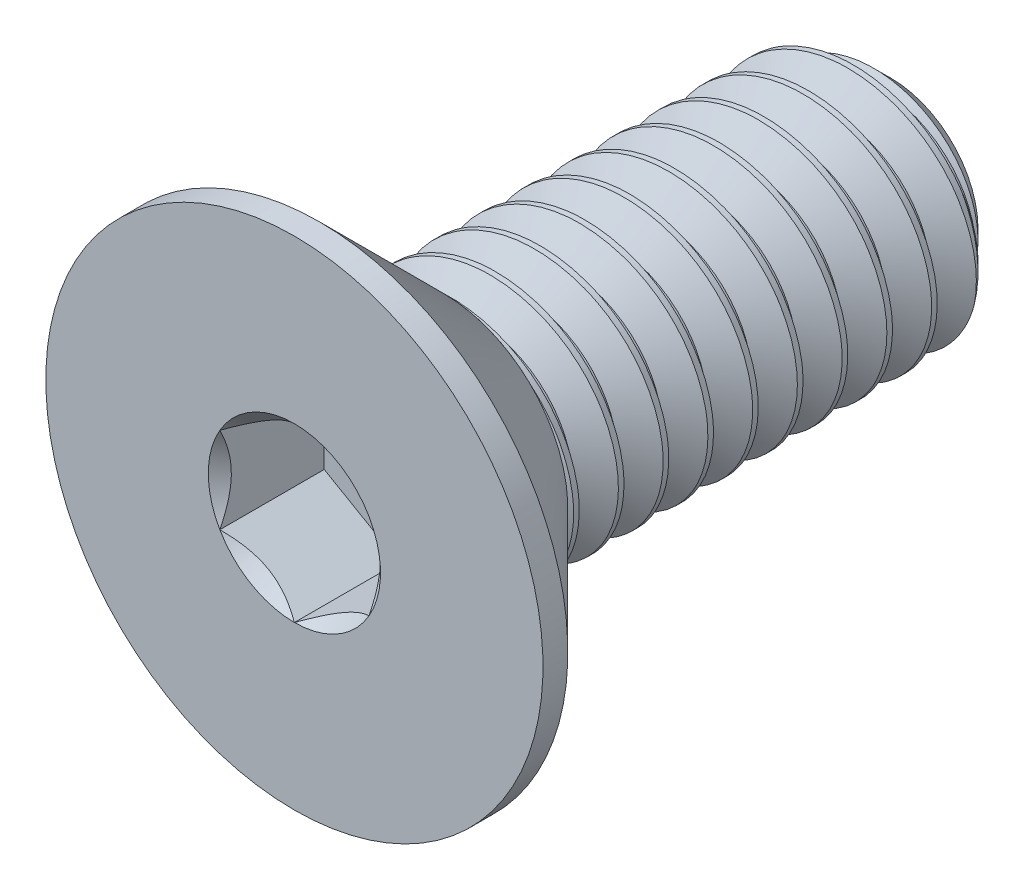
SolidWorks part; units mm, degrees
ref_plane "Front" through (0, 0, 0) normal (0, 0, 1) x (1, 0, 0)
ref_plane "Top" through (0, 0, 0) normal (0, 1, 0) x (1, 0, 0)
ref_plane "Right" through (0, 0, 0) normal (1, 0, 0) x (0, 0, -1)
sketch "Sketch1" plane through (0, 0, 0) normal (1, 0, 0) x (0, 0, -1)
  line L0 (-3, 2.5) -> (-2.75, 2.5) construction
  line L1 (-2.75, 2.5) -> (-1.5, 1.25) construction
  line L2 (-3, 1.25) -> (3, 1.25) construction
  line L3 (3, 1.25) -> (3, 0) construction
  line L4 (3, 0) -> (-3, 0) construction
  line L5 (-3, 0) -> (-3, 2.5) construction
  line L6 (-3, 2.5) -> (-3, -2.5) construction
  line L7 (3, 1.25) -> (3, -1.25) construction
  line L8 (-3, -2.5) -> (-2.75, -2.5) construction
  line L9 (-2.75, -2.5) -> (-1.5, -1.25) construction
  line L11 (-3, 1.25) -> (-3, 0) construction
  line L12 (-1.5, 1.25) -> (-1.5, 0) construction
  line L13 (2.9719, 1.2987) -> (3.1969, 0.909) construction
  line L14 (3.1969, 0.909) -> (3.4219, 1.2987) construction
  line L15 (3.4219, 1.2987) -> (2.9719, 1.2987) construction
  line L16 (3.1969, 1.2987) -> (3.1969, 1.25) construction
  line L17 (3.1969, 1.25) -> (3.1969, 0.9577) construction
  line L18 (3.1969, 0.9577) -> (3.1969, 0.909) construction
  line L19 (3.1969, 1.2744) -> (3.4078, 1.2744) construction
  line L20 (3.1969, 1.2744) -> (2.9859, 1.2744) construction
  line L21 (3, 1.25) -> (3.3938, 1.25) construction
  line L22 (3.1688, 0.9577) -> (3.225, 0.9577) construction
  line L23 (3, -1.25) -> (-1.5, -1.25) construction
  point P10 (1.875, -1.25)
  point P24 (-1.5, 1.25)
  point P30 (0, 0)
  dimension "Head Diameter" = 5
  dimension "Head Height" = 1.5
  dimension "Length" = 6
  dimension "Countersink Angle" = 90
  dimension "Thread Pitch" = 0.45
  dimension "D2" = 0.0563
  dimension "Minimum Thread Length" = 4.5
  dimension "Thread Size" = 2.5
  dimension "D1" = 1.125
sketch "Sketch2" plane through (0, 0, 0) normal (0, 0, 1) x (1, 0, 0)
  line L1 (0, 0.866) -> (-0.75, 0.433) construction
  line L2 (-0.75, 0.433) -> (-0.75, -0.433) construction
  line L3 (-0.75, -0.433) -> (0, -0.866) construction
  line L4 (0, -0.866) -> (0.75, -0.433) construction
  line L5 (0.75, -0.433) -> (0.75, 0.433) construction
  line L6 (0.75, 0.433) -> (0, 0.866) construction
  circle A0 centre (0, 0) radius 0.75 construction
  dimension "Drive Size" = 1.5
sketch "Sketch3" plane through (0, 0, 0) normal (1, 0, 0) x (0, 0, -1)
  line L0 (-3, 1.25) -> (3, 1.25)
  line L1 (3, 1.25) -> (3, 0)
  line L2 (3, 0) -> (-3, 0)
  line L3 (-3, 0) -> (-3, 1.25)
revolve "Revolve1" add sketch "Sketch3" angle 360 about L4
chamfer "Chamfer1" distance 0.375 angle 45 1 edges at (0, 1.25, -3)
sketch "Sketch6" plane through (0, 0, 0) normal (1, 0, 0) x (0, 0, -1)
  line L0 (-3, 2.5) -> (-2.75, 2.5)
  line L1 (-2.75, 2.5) -> (-1.5, 1.25)
  line L2 (-1.5, 1.25) -> (-1.5, 0)
  line L3 (-1.5, 0) -> (-3, 0)
  line L4 (-3, 0) -> (-3, 2.5)
revolve "Revolve2" add sketch "Sketch6" angle 360 about L4
sketch "Sketch8" plane through (0, 0, 3) normal (0, 0, 1) x (1, 0, 0)
  line L0 (0, 0.866) -> (-0.75, 0.433) construction
  line L1 (0.75, 0.433) -> (0, 0.866) construction
  line L2 (0.75, -0.433) -> (0.75, 0.433) construction
  line L3 (0, -0.866) -> (0.75, -0.433) construction
  line L4 (-0.75, 0.433) -> (-0.75, -0.433) construction
  line L5 (-0.75, -0.433) -> (0, -0.866) construction
  line L6 (0, 0.866) -> (-0.75, 0.433)
  line L7 (0.75, 0.433) -> (0, 0.866)
  line L8 (0.75, -0.433) -> (0.75, 0.433)
  line L9 (0, -0.866) -> (0.75, -0.433)
  line L10 (-0.75, 0.433) -> (-0.75, -0.433)
  line L11 (-0.75, -0.433) -> (0, -0.866)
extrude "Cut-Extrude1" cut sketch "Sketch8" against normal blind 1.05
sketch "Sketch9" plane through (0, 0, 3) normal (0, 0, 1) x (1, 0, 0)
  circle A0 centre (0, 0) radius 0.866
extrude "Cut-Extrude2" cut sketch "Sketch9" against normal up to next (1.05 mm away) draft 45
ref_plane "Plane1" through (0, 0, 1.5) normal (0, 0, 1) x (1, 0, 0)
split "Split1" trim tools "Plane1" bodies to split 124 resulting bodies 126 127
sketch "Sketch4" plane through (0, 0, -3) normal (0, 0, -1) x (-1, 0, 0)
  circle A0 centre (0, 0) radius 1.25 construction
  circle A1 centre (0, 0) radius 1.25
curve "Helix/Spiral1" pitch 0.45 height 4.95 radius 1.25 centre (0, 0, -3) axis (0, 0, 1) start towards (0, 1, 0)
sketch "Sketch10" plane through (0, 0, 0) normal (1, 0, 0) x (0, 0, -1)
  line L0 (2.9859, 1.2744) -> (3.4078, 1.2744)
  line L1 (3.4078, 1.2744) -> (3.225, 0.9577)
  line L2 (3.225, 0.9577) -> (3.1688, 0.9577)
  line L3 (3.1688, 0.9577) -> (2.9859, 1.2744)
sweep "Cut-Sweep1" cut profiles "Sketch10" path "Helix/Spiral1"
equation "\"D2@Sketch1\" = \"Thread Pitch@Sketch1\" / 8"
equation "\"D4@Helix/Spiral1\"=\"Thread Pitch@Sketch1\""
equation "\"D3@Helix/Spiral1\"=\"Minimum Thread Length@Sketch1\"+\"Thread Pitch@Sketch1\""
equation "\"D1@Chamfer1\"=\"Thread Size@Sketch1\"*.15"
equation "\"D1@Cut-Extrude1\"=\"Head Height@Sketch1\"*.7"
equation "\"D1@Sketch1\"=\"Thread Pitch@Sketch1\"*2.5"
